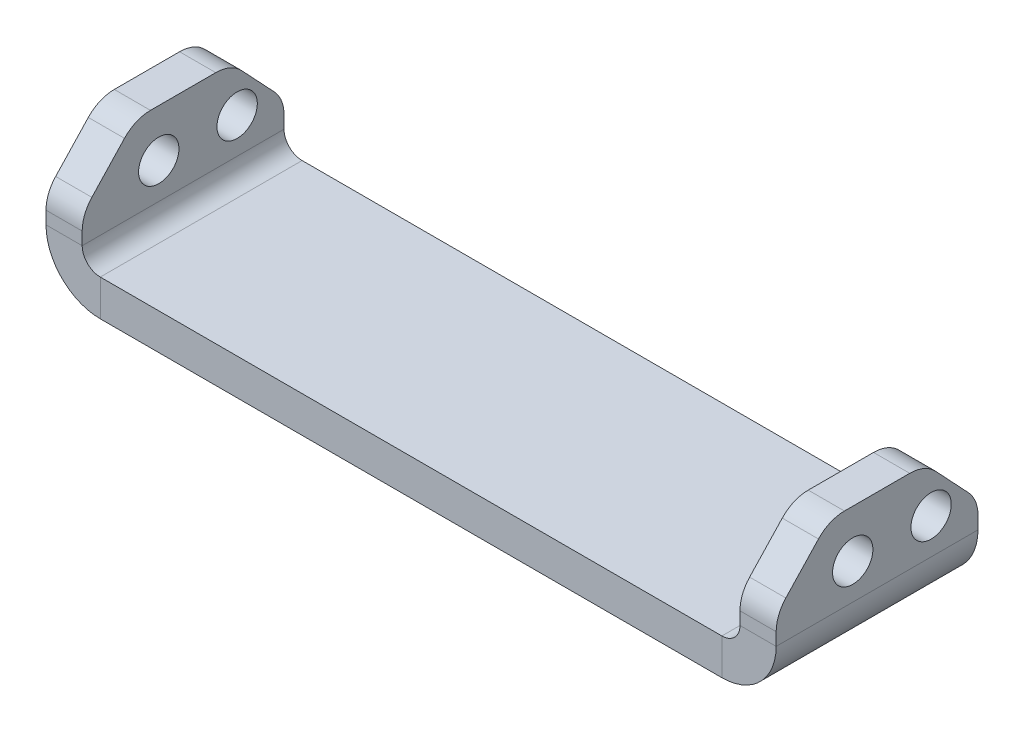
SolidWorks part; units mm, degrees
note: The reader was unsure of these and kept them because the rebuilt part matched: flange length of "Edge-Flange1".
ref_plane "Front Plane" through (0, 0, 0) normal (0, 0, 1) x (1, 0, 0)
ref_plane "Top Plane" through (0, 0, 0) normal (0, 1, 0) x (1, 0, 0)
ref_plane "Right Plane" through (0, 0, 0) normal (1, 0, 0) x (0, 0, -1)
sketch "Sketch1" plane through (0, 0, 0) normal (0, 1, 0) x (1, 0, 0)
  line L1 (0, 0) -> (15, 0)
  line L4 (15, 0) -> (15, 1.07)
  line L5 (0, 8.3) -> (0, 0)
  line L6 (13.4995, 3.6684) -> (6.1695, 7.8984)
  line L7 (4.67, 8.3) -> (0, 8.3)
  arc A0 (4.67, 8.3) -> (6.1695, 7.8984) centre (4.67, 5.3) cw
  arc A1 (13.4995, 3.6684) -> (15, 1.07) centre (12, 1.07) cw
  dimension "D2" = 3
  dimension "D1" = 15
  dimension "D3" = 8.3
  dimension "D4" = 1.07
  dimension "D5" = 4.67
sketch "Sketch20" plane through (0, 0, 0) normal (0, 1, 0) x (1, 0, 0)
  line L1 (0, 0) -> (61.5, 0)
  line L2 (0, 0) -> (0, 17)
  line L3 (0, 17) -> (61.5, 17)
  line L4 (61.5, 0) -> (61.5, 17)
  dimension "D1" = 17
  dimension "D2" = 61.5
base flange "Base-Flange1" sketch "Sketch20" thickness 3.048 reverse thickness direction no parameters "D1"=1.524
edge flange "Edge-Flange1" sketch "Sketch27" flange profiles "Sketch27", "Sketch28" flange angle 90 flange length 19 flange position material inside bend radius 1.524 thickness 3.048 relief rectangular parameters "D6"=10, "D8"=1
sketch "Sketch27" plane through (0, 0, 0) normal (-1, 0, 0) x (0, 0, 1)
  line L2 (-17, 0) -> (-17, 15.952)
  line L3 (-17, 15.952) -> (0, 15.952)
  line L4 (0, 15.952) -> (0, 0)
  line L11 (-17, 0) -> (0, 0) construction
  line L12 (-17, 0) -> (0, 0)
sketch "Sketch28" plane through (61.5, 0, 0) normal (1, 0, 0) x (0, 0, -1)
  line L0 (0, 0) -> (17, 0) construction
  line L1 (0, 0) -> (17, 0)
  line L2 (0, 0) -> (0, 15.952)
  line L3 (0, 15.952) -> (17, 15.952)
  line L4 (17, 15.952) -> (17, 0)
bend "EdgeBend1" bend radius 1.524 bend angle 90 parameters "D5"=1
bend "EdgeBend2" bend radius 1.524 bend angle 90 parameters "D5"=2
sketch "Sketch29" plane through (0, 0, 0) normal (1, 0, 0) x (0, 0, -1)
  line L0 (0, 1.524) -> (0, 2.594)
  line L1 (0, 15.952) -> (0, 1.524) construction
  line L2 (0.8126, 4.6471) -> (3.5626, 7.5771)
  line L3 (5.75, 8.524) -> (11.25, 8.524)
  line L4 (8.5, 1.524) -> (8.5, 17.0033) construction
  line L5 (21.7979, 1.524) -> (21.7979, 17.0033)
  line L6 (0, 1.524) -> (-4.7979, 1.524)
  line L7 (-4.7979, 1.524) -> (-4.7979, 17.0033)
  line L8 (-4.7979, 17.0033) -> (21.7979, 17.0033)
  line L9 (17, 1.524) -> (0, 1.524) construction
  line L10 (17, 1.524) -> (21.7979, 1.524)
  line L11 (16.1874, 4.6471) -> (13.4374, 7.5771)
  line L12 (17, 1.524) -> (17, 2.594)
  arc A0 (5.75, 8.524) -> (3.5626, 7.5771) centre (5.75, 5.524) ccw
  arc A1 (0.8126, 4.6471) -> (0, 2.594) centre (3, 2.594) ccw
  arc A2 (16.1874, 4.6471) -> (17, 2.594) centre (14, 2.594) cw
  arc A3 (11.25, 8.524) -> (13.4374, 7.5771) centre (11.25, 5.524) cw
  point P18 (0, 3.7813)
  point P21 (8.5, 8.524)
  point P28 (17, 3.7813)
  dimension "D1" = 3
  dimension "D2" = 1.07
  dimension "D3" = 5.5
  dimension "D4" = 7
extrude "Cut-Extrude3" cut sketch "Sketch29" against normal through all and the other way through all normal cut yes
hole_wizard "M3 Clearance Hole1" positions "3DSketch1" profile "Sketch30" hole size "M3" standard "ANSI Metric" end condition through all
sketch3d "3DSketch1"
  line L0 (0, 1.524, 0) -> (0, 1.524, -17) construction
  line L2 (0, 4.524, -13.05) -> (0, 4.524, -6.45) construction
  line L6 (0, 0, 0) -> (0, 50000, 0) construction
  point P0 (0, 4.524, -13.05)
  point P2 (0, 4.524, -6.45)
  dimension "D1" = 6.6
  dimension "D2" = 3
  dimension "D3" = 6.45
sketch "Sketch30" plane through (0, 4.524, -13.05) normal (0, 1, 0) x (0, 0, 1)
  line L0 (0, 0) -> (0, 61.5)
  line L1 (0, 61.5) -> (1.7, 61.5)
  line L2 (1.7, 61.5) -> (1.7, 0)
  line L5 (1.7, 0) -> (0, 0)
  line L11 (0, -6.35) -> (0, 107.95) construction
  dimension "Thru Hole Dia." = 3.4
  dimension "Thru Hole Depth" = 61.5
sketch "Bend-Lines3" [suppressed] plane through (0, 0, 0) normal (0, 1, 0) x (1, 0, 0)
sketch "Bounding-Box3" [suppressed] plane through (0, 0, 0) normal (0, 1, 0) x (1, 0, 0)
extrude "Cut-Extrude4" [suppressed] cut sketch "Sketch19" against normal through all
sketch "Sketch19" plane through (0, 0, 0) normal (0, 1, 0) x (1, 0, 0)
  line L0 (59.3219, 6.5) -> (59.3219, 8.5) construction
  line L1 (30.75, 15) -> (30.75, 0) construction
  line L2 (58.8219, 6.5) -> (58.8219, 8.5)
  line L3 (59.8219, 6.5) -> (59.8219, 8.5)
  line L4 (59.3219, 0) -> (59.3219, 15) construction
  line L5 (-6.2158, 15) -> (67.7158, 15) construction
  line L6 (-6.2158, 0) -> (67.7158, 0) construction
  line L7 (2.1781, 6.5) -> (2.1781, 8.5) construction
  line L8 (2.6781, 6.5) -> (2.6781, 8.5)
  line L9 (1.6781, 6.5) -> (1.6781, 8.5)
  arc A0 (58.8219, 6.5) -> (59.8219, 6.5) centre (59.3219, 6.5) ccw
  arc A1 (59.8219, 8.5) -> (58.8219, 8.5) centre (59.3219, 8.5) ccw
  arc A2 (2.6781, 6.5) -> (1.6781, 6.5) centre (2.1781, 6.5) cw
  arc A3 (1.6781, 8.5) -> (2.6781, 8.5) centre (2.1781, 8.5) cw
  point P4 (59.3219, 7.5)
  point P11 (2.1781, 7.5)
  dimension "D2" = 0.5
  dimension "D1" = 2
sheet metal parameters "Sheet-Metal8" thickness 3.048 parameters "D1"=1.524
flat pattern "Flat-Pattern8" [suppressed]
sketch "Bend-Lines4" plane through (0, 0, 0) normal (0, 1, 0) x (1, 0, 0)
sketch3d "Bounding-Box4" [suppressed]
  line L0 (-61.5, 15, 0) -> (0, 15, 0) construction
  line L1 (-61.5, 0, 0) -> (0, 0, 0) construction
  line L2 (-61.5, 15, 0) -> (-61.5, 0, 0) construction
  line L3 (0, 15, 0) -> (0, 0, 0) construction
sheet metal parameters "Sheet-Metal9" thickness 3.048 parameters "D1"=1.524
flat pattern "Flat-Pattern8"
sketch "Bend-Lines4" plane through (0, 0, 0) normal (0, 1, 0) x (1, 0, 0)
  line L0 (59.3219, 0) -> (59.3219, 15) construction
  line L1 (2.1781, 15) -> (2.1781, 0) construction
  line L2 (59.3219, 0) -> (59.3219, 15) construction
  line L3 (2.1781, 15) -> (2.1781, 0) construction
sketch3d "Bounding-Box4" [suppressed]
  line L0 (76.1438, 15, 0) -> (-14.6438, 15, 0) construction
  line L1 (76.1438, 0, 0) -> (-14.6438, 0, 0) construction
  line L2 (76.1438, 15, 0) -> (76.1438, 0, 0) construction
  line L3 (-14.6438, 15, 0) -> (-14.6438, 0, 0) construction
bend of the flat pattern "Flatten-<EdgeBend1>1"
bend of the flat pattern "Flatten-<EdgeBend2>1"
sheet metal parameters "Sheet-Metal10" thickness 3.048 parameters "D1"=1.524
flat pattern "Flat-Pattern8"
sketch "Bend-Lines4" plane through (0, 0, 0) normal (0, 1, 0) x (1, 0, 0)
  line L0 (59.3219, 0) -> (59.3219, 15) construction
  line L1 (2.1781, 15) -> (2.1781, 0) construction
  line L2 (59.3219, 0) -> (59.3219, 15) construction
  line L3 (2.1781, 15) -> (2.1781, 0) construction
sketch3d "Bounding-Box4" [suppressed]
  line L0 (-8.5158, 15, 0) -> (70.0158, 15, 0) construction
  line L1 (-8.5158, 0, 0) -> (70.0158, 0, 0) construction
  line L2 (-8.5158, 15, 0) -> (-8.5158, 0, 0) construction
  line L3 (70.0158, 15, 0) -> (70.0158, 0, 0) construction
bend of the flat pattern "Flatten-<EdgeBend1>1"
bend of the flat pattern "Flatten-<EdgeBend2>1"
sheet metal parameters "Sheet-Metal11" thickness 3.048 parameters "D1"=1.524
flat pattern "Flat-Pattern8"
sketch "Bend-Lines4" plane through (0, 0, 0) normal (0, 1, 0) x (1, 0, 0)
  line L0 (59.3219, 0) -> (59.3219, 17) construction
  line L1 (2.1781, 17) -> (2.1781, 0) construction
  line L2 (59.3219, 0) -> (59.3219, 17) construction
  line L3 (2.1781, 17) -> (2.1781, 0) construction
sketch3d "Bounding-Box4" [suppressed]
  line L0 (-7.2158, 17, 0) -> (68.7158, 17, 0) construction
  line L1 (-7.2158, 0, 0) -> (68.7158, 0, 0) construction
  line L2 (-7.2158, 17, 0) -> (-7.2158, 0, 0) construction
  line L3 (68.7158, 17, 0) -> (68.7158, 0, 0) construction
bend of the flat pattern "Flatten-<EdgeBend1>1"
bend of the flat pattern "Flatten-<EdgeBend2>1"
